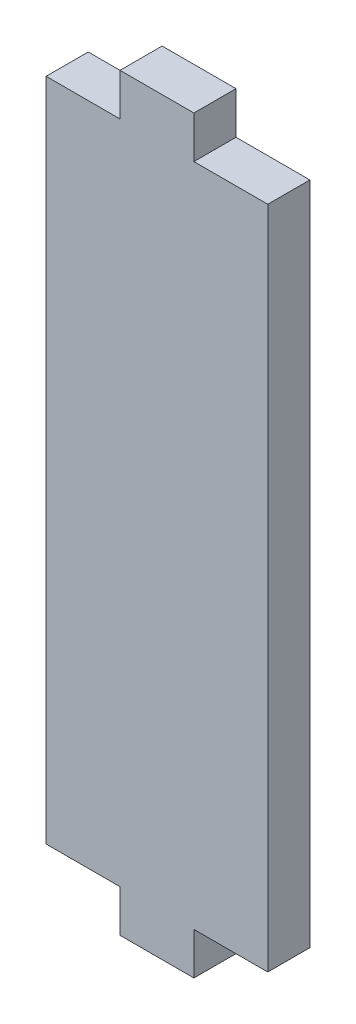
SolidWorks part; units mm, degrees
ref_plane "Front Plane" through (0, 0, 0) normal (0, 0, 1) x (1, 0, 0)
ref_plane "Top Plane" through (0, 0, 0) normal (0, 1, 0) x (1, 0, 0)
ref_plane "Right Plane" through (0, 0, 0) normal (1, 0, 0) x (0, 0, -1)
sketch "Sketch1" plane through (0, 0, 0) normal (0, 0, 1) x (1, 0, 0)
  line L1 (0, 0) -> (25.4, 0)
  line L2 (0, 0) -> (0, 85.852)
  line L3 (0, 85.852) -> (25.4, 85.852)
  line L4 (25.4, 0) -> (25.4, 85.852)
  dimension "D1" = 85.852
  dimension "D2" = 25.4
extrude "Boss-Extrude1" add sketch "Sketch1" along normal blind 4.826
sketch "Sketch2" plane through (0, 0, 4.826) normal (0, 0, 1) x (1, 0, 0)
  line L0 (0, 0) -> (25.4, 0) construction
  line L1 (0, 0) -> (8.4667, 0)
  line L2 (0, 0) -> (0, 4.826)
  line L3 (0, 4.826) -> (8.4667, 4.826)
  line L4 (8.4667, 0) -> (8.4667, 4.826)
  line L5 (8.4667, 4.826) -> (16.9333, 4.826) construction
  line L6 (0, 42.926) -> (25.4, 42.926) construction
  line L7 (0, 85.852) -> (0, 0) construction
  line L8 (8.4667, 81.026) -> (16.9333, 81.026) construction
  line L9 (25.4, 0) -> (25.4, 85.852) construction
  line L10 (16.9333, 0) -> (25.4, 0)
  line L11 (16.9333, 0) -> (16.9333, 4.826)
  line L12 (16.9333, 4.826) -> (25.4, 4.826)
  line L13 (25.4, 0) -> (25.4, 4.826)
  line L14 (25.4, 85.852) -> (25.4, 81.026)
  line L15 (16.9333, 81.026) -> (25.4, 81.026)
  line L16 (16.9333, 85.852) -> (16.9333, 81.026)
  line L17 (16.9333, 85.852) -> (25.4, 85.852)
  line L18 (8.4667, 85.852) -> (8.4667, 81.026)
  line L19 (0, 81.026) -> (8.4667, 81.026)
  line L20 (0, 85.852) -> (0, 81.026)
  line L21 (0, 85.852) -> (8.4667, 85.852)
  dimension "D1" = 4.826
extrude "Cut-Extrude1" cut sketch "Sketch2" against normal through all
equation "\"MDF\"= 0.19in"
equation "\"PVCID\" = 2.067in"
equation "\"PVCOD\" = 2.375in"
equation "\"GenDiameter\"= 60mm"
equation "\"GenCutDiameter\" = 1.8in"
equation "\"GenCutDistance\" = 1"
equation "\"TowerHeight\" = 6in"
equation "\"TowerFrontBase\" = 3in"
equation "\"FunnelHeight\" = 1in"
equation "\"FunnelAngle\" = 20"
equation "\"TowerSideBase\" = 3in"
equation "\"TowerPanelLength\" = 2in"
equation "\"TowerPanelLeeway\" = 0.5in"
equation "\"BaseLength\" = 9in"
equation "\"BaseWidth\" = 10in"
equation "\"WheelHoleLength\" = 3.25in"
equation "\"WheelHoleWidth\" = 26mm"
equation "\"WheelHoleFromBack\" = 1.5in"
equation "\"DropLength\" = 1in"
equation "\"DropWidth\" = 8.5in"
equation "\"BumperWidth\" = 1in"
equation "\"SmallHexDiameter\" = 0.185in"
equation "\"SmallHexHeight\" = 0.701in"
equation "\"ScrewSize\" = 0.106in"
equation "\"BigHexDiameter\" = 0.251in"
equation "\"BigHexHeight\" = 0.374in"
equation "\"PCBThickness\" = 0.066in"
equation "\"ConnectorHeight\" = 0.517in"
equation "\"BoardHeight\" = 0.583in"
equation "\"UnoStackHeight\" = 1.351in"
equation "\"UnoStackWidth\" = 3.053in"
equation "\"UnoStackLength\" = 3.152in"
equation "\"HBridgeWidth\" = 1.797in"
equation "\"HBridgeLength\" = 2.236in"
equation "\"DSWidth\" = 1.820in"
equation "\"DSLength\" = 1.833in"
equation "\"StepperWidth\" = 1.799in"
equation "\"StepperLength\" = 2.248in"
equation "\"ULNWidth\" = 1.304in"
equation "\"ULNLength\" = 1.545in"
equation "\"VSwitchHeight\" = 0.392in"
equation "\"VSwitchWidth\" = 0.637in"
equation "\"VSwitchLength\" = 1.097in"
equation "\"SkateWheelDiameter\" = 80mm"
equation "\"SkateWheelThickness\" = 24mm"
equation "\"BaseDistance\" = 3in"
equation "\"DummyVar\" = 2in"
equation "\"D1@Sketch1\"=2*\"MDF\"+3in"
equation "\"D1@Boss-Extrude1\"=\"MDF\""
equation "\"D1@Sketch2\"=\"MDF\""
